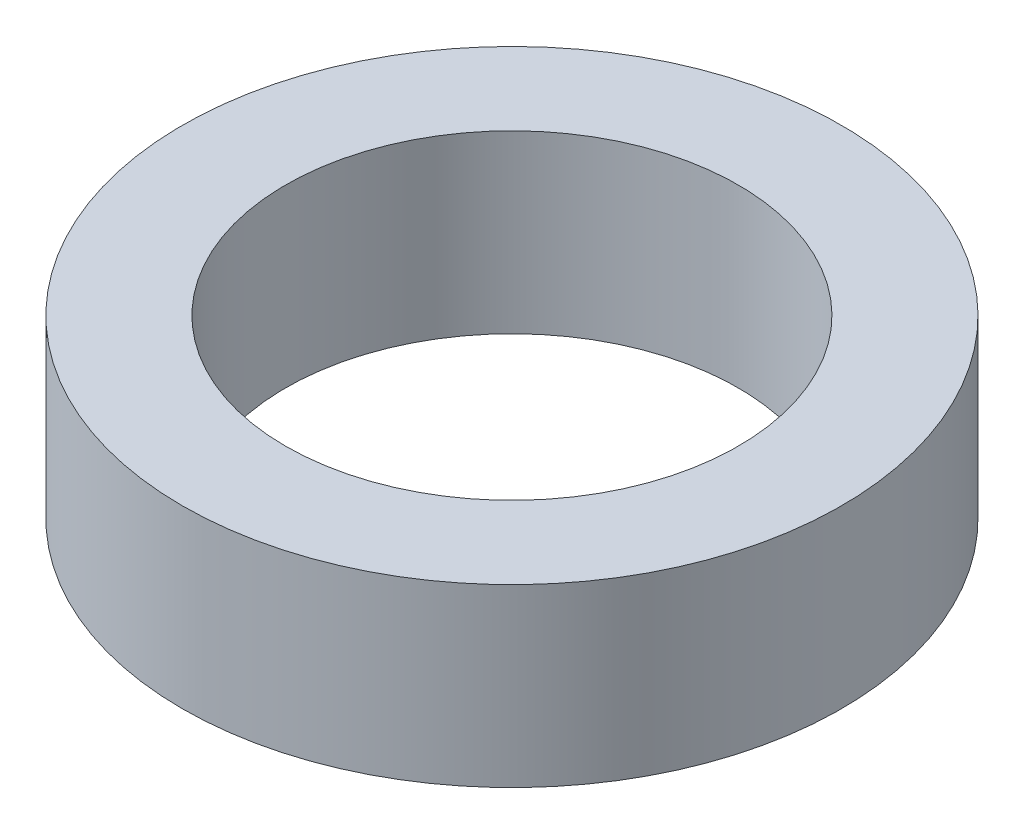
SolidWorks part; units mm, degrees
ref_plane "Front Plane" through (0, 0, 0) normal (0, 0, 1) x (1, 0, 0)
ref_plane "Top Plane" through (0, 0, 0) normal (0, 1, 0) x (1, 0, 0)
ref_plane "Right Plane" through (0, 0, 0) normal (1, 0, 0) x (0, 0, -1)
sketch "Sketch1" plane through (0, 0, 0) normal (0, 1, 0) x (1, 0, 0)
  circle A0 centre (0, 0) radius 7.5
  dimension "D1" = 15
extrude "Boss-Extrude1" add sketch "Sketch1" along normal blind 4
sketch "Sketch2" plane through (0, 4, 0) normal (0, 1, 0) x (1, 0, 0)
  circle A0 centre (0, 0) radius 5.15
  dimension "D1" = 10.3
extrude "Cut-Extrude1" cut sketch "Sketch2" against normal blind 4
